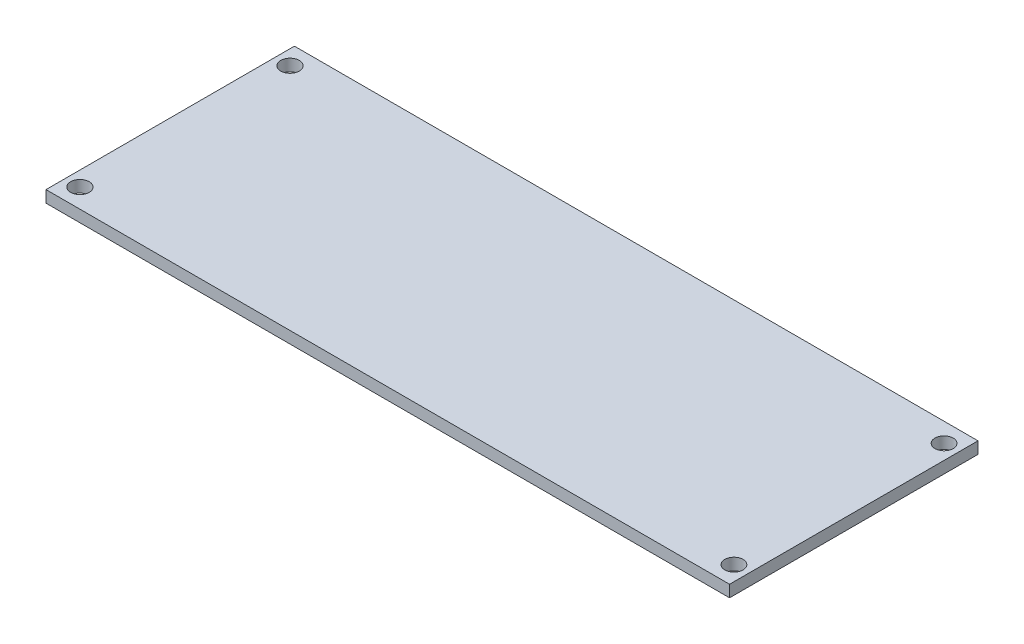
SolidWorks part; units mm, degrees
ref_plane "前视基准面" through (0, 0, 0) normal (0, 0, 1) x (1, 0, 0)
ref_plane "上视基准面" through (0, 0, 0) normal (0, 1, 0) x (1, 0, 0)
ref_plane "右视基准面" through (0, 0, 0) normal (1, 0, 0) x (0, 0, -1)
sketch "草图2" plane through (0, 0, 0) normal (0, 1, 0) x (1, 0, 0)
  line L0 (-58, 21.08) -> (58, 21.08)
  line L1 (-60, 23.08) -> (60, 23.08)
  line L2 (-60, 23.08) -> (-60, -23.08)
  line L3 (-60, -23.08) -> (60, -23.08)
  line L4 (60, 23.08) -> (60, -23.08)
  line L5 (58, 21.08) -> (58, -21.08)
  line L6 (-58, -21.08) -> (58, -21.08)
  line L7 (-58, 21.08) -> (-58, -21.08)
  point P4 (0, 23.08)
  point P6 (60, 0)
  dimension "D1" = 120
  dimension "D2" = 46.16
  dimension "D3" = 2
extrude "凸台-拉伸1" add sketch "草图2" along normal blind 23.1
sketch "草图3" plane through (0, 23.1, 0) normal (0, 1, 0) x (1, 0, 0)
  line L0 (-60, -23.08) -> (60, -23.08) construction
  line L2 (-47.75, 21.05) -> (-47.75, -21.05)
  line L4 (47.75, 21.05) -> (47.75, -21.05)
  line L5 (60, 23.08) -> (-60, 23.08) construction
  line L6 (-42.75, 23.08) -> (-38.75, 23.08)
  line L7 (-42.75, 23.08) -> (-42.75, 17.08)
  line L8 (-42.75, 17.08) -> (-38.75, 17.08)
  line L9 (-38.75, 23.08) -> (-38.75, 17.08)
  line L10 (-42.75, -23.08) -> (-38.75, -23.08)
  line L11 (-42.75, -23.08) -> (-42.75, -17.08)
  line L12 (-42.75, -17.08) -> (-38.75, -17.08)
  line L13 (-38.75, -23.08) -> (-38.75, -17.08)
  line L15 (26.35, 23.08) -> (30.35, 23.08)
  line L16 (26.35, 23.08) -> (26.35, 18.08)
  line L17 (26.35, 18.08) -> (30.35, 18.08)
  line L18 (30.35, 23.08) -> (30.35, 18.08)
  line L19 (26.35, -23.08) -> (30.35, -23.08)
  line L20 (26.35, -23.08) -> (26.35, -18.08)
  line L21 (26.35, -18.08) -> (30.35, -18.08)
  line L22 (30.35, -23.08) -> (30.35, -18.08)
  point P6 (47.75, 0)
  dimension "D1" = 95.5
  dimension "D2" = 42.1
  dimension "D3" = 4
  dimension "D4" = 6
  dimension "D5" = 5
  dimension "D6" = 6
  dimension "D7" = 4
  dimension "D8" = 5
  dimension "D9" = 5
  dimension "D10" = 21.4
  dimension "D11" = 4
  dimension "D12" = 4
  dimension "D13" = 5
  dimension "D14" = 21.4
extrude "凸台-拉伸3" add sketch "草图3" along normal blind 4.1 contours L18 L17 L16 L15 | L22 L21 L20 L19 | L13 L12 L11 L10 | L9 L8 L7 L6
sketch "草图4" plane through (0, 23.1, 0) normal (0, 1, 0) x (1, 0, 0)
  line L0 (-42.75, 21.08) -> (-58, 21.08) construction
  line L1 (-47.75, 21.08) -> (47.75, 21.08)
  line L2 (-47.75, 21.08) -> (-47.75, -21.08)
  line L3 (-47.75, -21.08) -> (47.75, -21.08)
  line L4 (47.75, 21.08) -> (47.75, -21.08)
  line L5 (30.35, -21.08) -> (58, -21.08) construction
  line L6 (60, 23.08) -> (30.35, 23.08) construction
  line L7 (32.55, 23.08) -> (45.75, 23.08)
  line L8 (32.55, 23.08) -> (32.55, 21.08)
  line L9 (32.55, 21.08) -> (45.75, 21.08)
  line L10 (45.75, 23.08) -> (45.75, 21.08)
  line L16 (-38.75, 23.08) -> (-42.75, 23.08)
  line L17 (-42.75, 23.08) -> (-42.75, 17.08)
  line L18 (-42.75, 17.08) -> (-38.75, 17.08)
  line L19 (-38.75, 17.08) -> (-38.75, 23.08)
  line L20 (-58, 21.08) -> (-42.75, 21.08)
  line L21 (-42.75, 21.08) -> (-42.75, 23.08)
  line L22 (-42.75, 23.08) -> (-60, 23.08)
  line L23 (-60, 23.08) -> (-60, -23.08)
  line L24 (-60, -23.08) -> (-42.75, -23.08)
  line L25 (-42.75, -23.08) -> (-42.75, -21.08)
  line L26 (-42.75, -21.08) -> (-58, -21.08)
  line L27 (-58, -21.08) -> (-58, 21.08)
  line L28 (-58, 21.08) -> (-42.75, 21.08)
  line L29 (-42.75, 21.08) -> (-42.75, 23.08)
  line L30 (-42.75, 23.08) -> (-60, 23.08)
  line L31 (-60, 23.08) -> (-60, -23.08)
  line L32 (-60, -23.08) -> (-42.75, -23.08)
  line L33 (-42.75, -23.08) -> (-42.75, -21.08)
  line L34 (-42.75, -21.08) -> (-58, -21.08)
  line L35 (-58, -21.08) -> (-58, 21.08)
  line L36 (-38.75, 23.08) -> (-42.75, 23.08)
  line L37 (-42.75, 23.08) -> (-42.75, 17.08)
  line L38 (-42.75, 17.08) -> (-38.75, 17.08)
  line L39 (-38.75, 17.08) -> (-38.75, 23.08)
  line L40 (-38.75, 23.08) -> (-38.75, 21.08)
  line L41 (-38.75, 21.08) -> (26.35, 21.08)
  line L42 (26.35, 21.08) -> (26.35, 23.08)
  line L43 (26.35, 23.08) -> (-38.75, 23.08)
  line L44 (-38.75, 23.08) -> (-38.75, 21.08)
  line L45 (-38.75, 21.08) -> (26.35, 21.08)
  line L46 (26.35, 21.08) -> (26.35, 23.08)
  line L47 (26.35, 23.08) -> (-38.75, 23.08)
  line L48 (30.35, 23.08) -> (26.35, 23.08)
  line L49 (26.35, 23.08) -> (26.35, 18.08)
  line L50 (26.35, 18.08) -> (30.35, 18.08)
  line L51 (30.35, 18.08) -> (30.35, 23.08)
  line L52 (30.35, 23.08) -> (26.35, 23.08)
  line L53 (26.35, 23.08) -> (26.35, 18.08)
  line L54 (26.35, 18.08) -> (30.35, 18.08)
  line L55 (30.35, 18.08) -> (30.35, 23.08)
  line L56 (26.35, -23.08) -> (30.35, -23.08)
  line L57 (30.35, -23.08) -> (30.35, -18.08)
  line L58 (30.35, -18.08) -> (26.35, -18.08)
  line L59 (26.35, -18.08) -> (26.35, -23.08)
  line L60 (58, -21.08) -> (30.35, -21.08)
  line L61 (30.35, -21.08) -> (30.35, -23.08)
  line L62 (30.35, -23.08) -> (60, -23.08)
  line L63 (60, -23.08) -> (60, 23.08)
  line L64 (60, 23.08) -> (30.35, 23.08)
  line L65 (30.35, 23.08) -> (30.35, 21.08)
  line L66 (30.35, 21.08) -> (58, 21.08)
  line L67 (58, 21.08) -> (58, -21.08)
  line L68 (58, -21.08) -> (30.35, -21.08)
  line L69 (30.35, -21.08) -> (30.35, -23.08)
  line L70 (30.35, -23.08) -> (60, -23.08)
  line L71 (60, -23.08) -> (60, 23.08)
  line L72 (60, 23.08) -> (30.35, 23.08)
  line L73 (30.35, 23.08) -> (30.35, 21.08)
  line L74 (30.35, 21.08) -> (58, 21.08)
  line L75 (58, 21.08) -> (58, -21.08)
  line L76 (26.35, -23.08) -> (30.35, -23.08)
  line L77 (30.35, -23.08) -> (30.35, -18.08)
  line L78 (30.35, -18.08) -> (26.35, -18.08)
  line L79 (26.35, -18.08) -> (26.35, -23.08)
  line L81 (22.55, 23.08) -> (15.05, 23.08)
  line L82 (22.55, 23.08) -> (22.55, 21.08)
  line L83 (22.55, 21.08) -> (15.05, 21.08)
  line L87 (26.35, -21.08) -> (-38.75, -21.08)
  line L88 (-38.75, -21.08) -> (-38.75, -23.08)
  line L89 (-38.75, -23.08) -> (26.35, -23.08)
  line L90 (26.35, -23.08) -> (26.35, -21.08)
  line L91 (26.35, -21.08) -> (-38.75, -21.08)
  line L92 (-42.75, -23.08) -> (-38.75, -23.08)
  line L93 (-38.75, -23.08) -> (-38.75, -17.08)
  line L94 (-38.75, -17.08) -> (-42.75, -17.08)
  line L95 (-42.75, -17.08) -> (-42.75, -23.08)
  line L96 (-42.75, -23.08) -> (-38.75, -23.08)
  line L97 (-38.75, -23.08) -> (-38.75, -17.08)
  line L98 (-38.75, -17.08) -> (-42.75, -17.08)
  line L99 (-42.75, -17.08) -> (-42.75, -23.08)
  line L100 (15.05, 23.08) -> (15.05, 21.08)
  line L101 (-38.75, -21.08) -> (-38.75, -23.08)
  line L102 (-38.75, -23.08) -> (26.35, -23.08)
  line L103 (26.35, -23.08) -> (26.35, -21.08)
  point P8 (0, 21.08)
  line M45 (58, -21.08) -> (30.35, -21.08)
  line M46 (30.35, -21.08) -> (30.35, -23.08)
  line M47 (30.35, -23.08) -> (60, -23.08)
  line M48 (60, -23.08) -> (60, 23.08)
  line M49 (60, 23.08) -> (30.35, 23.08)
  line M50 (30.35, 23.08) -> (30.35, 21.08)
  line M51 (30.35, 21.08) -> (58, 21.08)
  line M52 (58, 21.08) -> (58, -21.08)
  dimension "D1" = 95.5
  dimension "D2" = 2
  dimension "D3" = 13.2
  dimension "D12" = 25.2
  dimension "D13" = 7.5
  dimension "D4" = 0
  dimension "D5" = 0
  dimension "D6" = 0
  dimension "D7" = 0
  dimension "D8" = 0
  dimension "D9" = 0
  dimension "D10" = 0
  dimension "D11" = 0
extrude "凸台-拉伸4" add sketch "草图4" along normal blind 5.5 contours L34 L35 L28 L1 L29 L30 L31 L32 L33 L3 | L96 L97 L3 L33 | L97 L102 L79 L3 | L3 L79 L76 M46 | L10 M49 M51 M52 M45 M46 M47 M48 | L8 M49 M50 M51 | L52 L46 L1 M50 | L47 L82 L45 L46 | L100 L47 L39 L1 | L1 L39 L36 L29 region at (-52.875, 23.1, -21.5728) region at (-40.75, 23.1, -22.08) region at (-11.85, 23.1, -22.08) region at (-40.75, 23.1, 22.08) region at (-6.2, 23.1, 22.08) region at (24.45, 23.1, -22.08) region at (28.35, 23.1, 22.08) region at (28.35, 23.1, -22.08) region at (39.05, 23.1, 21.6286) region at (31.45, 23.1, -22.08)
sketch "草图7" plane through (0, 0, -21.08) normal (0, 0, 1) x (1, 0, 0)
  line L1 (22.55, 28.6) -> (15.05, 28.6)
  line L2 (22.55, 28.6) -> (22.55, 26.6)
  line L3 (22.55, 26.6) -> (15.05, 26.6)
  line L4 (15.05, 28.6) -> (15.05, 26.6)
  line L12 (22.55, 23.1) -> (15.05, 23.1)
  line L13 (15.05, 23.1) -> (15.05, 28.6)
  line L14 (15.05, 28.6) -> (-58, 28.6)
  line L15 (-58, 28.6) -> (-58, 0)
  line L16 (-58, 0) -> (58, 0)
  line L17 (58, 0) -> (58, 28.6)
  line L18 (58, 28.6) -> (45.75, 28.6)
  line L19 (45.75, 28.6) -> (45.75, 23.1)
  line L20 (45.75, 23.1) -> (32.55, 23.1)
  line L21 (32.55, 23.1) -> (32.55, 28.6)
  line L22 (32.55, 28.6) -> (22.55, 28.6)
  line L23 (22.55, 28.6) -> (22.55, 23.1)
  line L24 (22.55, 23.1) -> (15.05, 23.1)
  line L25 (15.05, 23.1) -> (15.05, 28.6)
  line L26 (15.05, 28.6) -> (-58, 28.6)
  line L27 (-58, 28.6) -> (-58, 0)
  line L28 (-58, 0) -> (58, 0)
  line L29 (58, 0) -> (58, 28.6)
  line L30 (58, 28.6) -> (45.75, 28.6)
  line L31 (45.75, 28.6) -> (45.75, 23.1)
  line L32 (45.75, 23.1) -> (32.55, 23.1)
  line L33 (32.55, 23.1) -> (32.55, 28.6)
  line L34 (32.55, 28.6) -> (22.55, 28.6)
  line L35 (22.55, 28.6) -> (22.55, 23.1)
  line M15 (15.05, 23.1) -> (15.05, 28.6)
  line M25 (22.55, 28.6) -> (22.55, 23.1)
  dimension "D2" = 2
  dimension "D1" = 0
extrude "凸台-拉伸5" add sketch "草图7" against normal blind 1 contours L3 L1 M25 M15 region at (18.8, 27.6, -21.08)
sketch "草图8" plane through (0, 0, -23.08) normal (0, 0, -1) x (-1, 0, 0)
  line L1 (-22.55, 23.1) -> (-15.05, 23.1)
  line L2 (-22.55, 23.1) -> (-22.55, 21.1)
  line L3 (-22.55, 21.1) -> (-15.05, 21.1)
  line L4 (-15.05, 23.1) -> (-15.05, 21.1)
  line L5 (-22.55, 28.6) -> (-26.55, 28.6)
  line L6 (-22.55, 28.6) -> (-22.55, 21.1)
  line L7 (-22.55, 21.1) -> (-26.55, 21.1)
  line L8 (-26.55, 28.6) -> (-26.55, 21.1)
  line L9 (-15.05, 28.6) -> (-11.05, 28.6)
  line L10 (-15.05, 28.6) -> (-15.05, 21.1)
  line L11 (-15.05, 21.1) -> (-11.05, 21.1)
  line L12 (-11.05, 28.6) -> (-11.05, 21.1)
  line M4 (-15.05, 28.6) -> (-15.05, 23.1)
  line M5 (-15.05, 23.1) -> (-22.55, 23.1)
  line M6 (-22.55, 23.1) -> (-22.55, 28.6)
  line M7 (-22.55, 28.6) -> (-32.55, 28.6)
  line M15 (60, 28.6) -> (-15.05, 28.6)
  dimension "D1" = 2
  dimension "D2" = 4
  dimension "D3" = 4
extrude "切除-拉伸1" cut sketch "草图8" against normal blind 1 contours L8 L7 L2 M7 M6 | L4 L2 L3 M5 | L12 L4 L11 M15 M4 region at (18.8, 22.1, -23.08) region at (24.55, 24.85, -23.08) region at (13.05, 24.85, -23.08)
sketch "草图9" plane through (0, 28.6, 0) normal (0, 1, 0) x (1, 0, 0)
  line L0 (18.8, 22.6917) -> (18.8, 20.4523)
  line L4 (22.55, 21.08) -> (22.55, 22.08)
  line L5 (22.55, 22.08) -> (15.05, 22.08)
  line L6 (15.05, 22.08) -> (15.05, 21.08)
  line L7 (15.05, 21.08) -> (22.55, 21.08)
  line L8 (22.55, 21.08) -> (22.55, 22.08)
  line L9 (22.55, 22.08) -> (15.05, 22.08)
  line L10 (15.05, 22.08) -> (15.05, 21.08)
  line L11 (15.05, 21.08) -> (22.55, 21.08)
  spline S0 degree 2 poles (11.05, 23.08) (12.6234, 21.9645) (15.05, 22.08) knots 0 0 0 1 1 1
  spline S1 degree 2 poles (26.55, 23.08) (24.9766, 21.9645) (22.55, 22.08) knots 0 0 0 1 1 1
  point P5 (18.8, 22.08)
  line M6 (26.55, 23.08) -> (26.55, 22.08)
  line M7 (26.55, 22.08) -> (11.05, 22.08)
  line M8 (11.05, 22.08) -> (11.05, 23.08)
  dimension "D1" = 0
extrude "凸台-拉伸6" add sketch "草图9" against normal up to surface (7.5 mm away) contours S0 M8 M7 | S1 M6 M7 region at (25.7395, 28.6, -22.3711) region at (11.8605, 28.6, -22.3711) up to face at (18.8, 21.1, -22.58)
sketch "草图10" plane through (0, 28.6, 0) normal (0, 1, 0) x (1, 0, 0)
  line L1 (-60, 23.08) -> (60, 23.08)
  line L2 (-60, 23.08) -> (-60, -23.08)
  line L3 (-60, -23.08) -> (60, -23.08)
  line L4 (60, 23.08) -> (60, -23.08)
  line L5 (-58, 21.08) -> (58, 21.08)
  line L6 (-58, 21.08) -> (-58, -21.08)
  line L7 (-58, -21.08) -> (58, -21.08)
  line L8 (58, 21.08) -> (58, -21.08)
extrude "凸台-拉伸7" add sketch "草图10" along normal blind 2
sketch "草图11" plane through (0, 0, -21.08) normal (0, 0, 1) x (1, 0, 0)
  line L0 (45.75, 23.1) -> (32.55, 23.1) construction
  line L1 (45.75, 23.1) -> (32.55, 23.1)
  line L2 (58, 0) -> (-58, 0) construction
  line L3 (36.11, 23.1) -> (39.11, 23.1)
  line L4 (36.11, 23.1) -> (36.11, 0)
  line L5 (36.11, 0) -> (39.11, 0)
  line L6 (39.11, 23.1) -> (39.11, 0)
  line M6 (-58, 0) -> (58, 0)
  dimension "D1" = 9.64
  dimension "D2" = 3
extrude "切除-拉伸2" cut sketch "草图11" against normal blind 1.5 contours L6 L1 L4 M6 region at (37.61, 11.55, -21.08)
sketch "草图12" plane through (0, 30.6, 0) normal (0, 1, 0) x (1, 0, 0)
  line L1 (-60, 23.08) -> (60, 23.08)
  line L2 (-60, 23.08) -> (-60, -23.08)
  line L3 (-60, -23.08) -> (60, -23.08)
  line L4 (60, 23.08) -> (60, -23.08)
extrude "凸台-拉伸8" add sketch "草图12" along normal blind 2
sketch "草图13" plane through (0, 32.6, 0) normal (0, 1, 0) x (1, 0, 0)
  line L0 (-58, 21.08) -> (-58, -21.08) construction
  line L1 (58, -21.08) -> (58, 21.08) construction
  line L2 (-58, -21.08) -> (58, -21.08) construction
  line L3 (36.11, 21.08) -> (-58, 21.08) construction
  line L4 (-58, 21.08) -> (-58, -21.08)
  line L5 (58, -21.08) -> (58, 21.08)
  line L6 (-58, -21.08) -> (58, -21.08)
  line L7 (36.11, 21.08) -> (-58, 21.08)
  line L8 (36.11, 21.08) -> (58, 21.08)
  line L10 (-58, 21.08) -> (58, 21.08)
  line L11 (-58, 21.08) -> (-58, 8.08)
  line L12 (-58, 8.08) -> (58, 8.08)
  line L13 (58, 21.08) -> (58, 8.08)
  circle A0 centre (38.25, -12.68) radius 3.5
  dimension "D2" = 7
  dimension "D1" = 13
  dimension "D3" = 19.75
  dimension "D4" = 8.4
extrude "切除-拉伸3" cut sketch "草图13" against normal blind 2 contours L4 L12 L5 L8 L7 | A0 region at (0, 32.6, -14.58) region at (38.25, 32.6, 12.68)
sketch "草图14" plane through (-58, 0, 0) normal (1, 0, 0) x (0, 0, -1)
  line L0 (30.1627, 64.1374) -> (36.3882, 59.7782)
  line L1 (8.08, 32.6) -> (30.1627, 64.1374)
  line L2 (36.3882, 59.7782) -> (17.3579, 32.6)
  line L3 (19.7994, 32.6) -> (38.6001, 59.4502)
  line L4 (19.7994, 32.6) -> (17.3579, 32.6)
  line L5 (38.6001, 59.4502) -> (29.9171, 65.5301)
  line L6 (29.9171, 65.5301) -> (6.8592, 32.6)
  line L7 (-21.08, 0) -> (21.08, 0)
  line L8 (21.08, 0) -> (21.08, 32.6)
  line L9 (21.08, 32.6) -> (8.08, 32.6)
  line L10 (8.08, 32.6) -> (8.08, 30.6)
  line L11 (8.08, 30.6) -> (-21.08, 30.6)
  line L12 (-21.08, 30.6) -> (-21.08, 0)
  line L15 (19.7994, 32.6) -> (8.08, 32.6)
  line L19 (6.8592, 32.6) -> (8.08, 32.6)
  line L20 (8.08, 32.6) -> (6.8592, 32.6)
  line M14 (21.08, 32.6) -> (8.08, 32.6)
  dimension "D2" = 38.5
  dimension "D3" = 7.6
  dimension "D4" = 2
  dimension "D5" = 1
  dimension "D6" = 55
  dimension "D7" = 1
  dimension "D1" = 0
extrude "凸台-拉伸15" add sketch "草图14" along normal up to surface (116 mm away) separate body contours L6 L19 L1 L0 L2 L3 L5 M14 region at (-58, 48.631, -18.7467) up to face at (58, 21.0667, -2.6933)
sketch "草图15" plane through (58, 0, 0) normal (1, 0, 0) x (0, 0, -1)
  line L0 (19.7994, 32.6) -> (6.8592, 32.6)
  line L8 (6.8592, 32.6) -> (8.08, 32.6)
  line L9 (8.08, 32.6) -> (30.1627, 64.1374)
  line L10 (30.1627, 64.1374) -> (36.3882, 59.7782)
  line L11 (36.3882, 59.7782) -> (17.3579, 32.6)
  line L12 (17.3579, 32.6) -> (19.7994, 32.6)
  line L13 (19.7994, 32.6) -> (38.6001, 59.4502)
  line L14 (38.6001, 59.4502) -> (29.9171, 65.5301)
  line L15 (29.9171, 65.5301) -> (6.8592, 32.6)
  line L16 (6.8592, 32.6) -> (8.08, 32.6)
  line L17 (8.08, 32.6) -> (30.1627, 64.1374)
  line L18 (30.1627, 64.1374) -> (36.3882, 59.7782)
  line L19 (36.3882, 59.7782) -> (17.3579, 32.6)
  line L20 (17.3579, 32.6) -> (19.7994, 32.6)
  line L21 (19.7994, 32.6) -> (38.6001, 59.4502)
  line L22 (38.6001, 59.4502) -> (29.9171, 65.5301)
  line L23 (29.9171, 65.5301) -> (6.8592, 32.6)
  line M9 (6.8592, 32.6) -> (8.08, 32.6)
  line M10 (8.08, 32.6) -> (30.1627, 64.1374)
  line M11 (30.1627, 64.1374) -> (36.3882, 59.7782)
  line M12 (36.3882, 59.7782) -> (17.3579, 32.6)
  line M13 (17.3579, 32.6) -> (19.7994, 32.6)
  line M14 (19.7994, 32.6) -> (38.6001, 59.4502)
  line M15 (38.6001, 59.4502) -> (29.9171, 65.5301)
  line M16 (29.9171, 65.5301) -> (6.8592, 32.6)
  dimension "D1" = 0
extrude "凸台-拉伸17" add sketch "草图15" along normal up to surface (2 mm away) separate body contours M16 M9 M10 M11 M12 M13 M14 M15 | L0 M12 M11 M10 region at (58, 33.0574, -18.5787) region at (58, 47.3059, -22.9013) up to face at (60, 16.3, 0)
sketch "草图16" plane through (-58, 0, 0) normal (-1, 0, 0) x (0, 0, 1)
  line L0 (-19.7994, 32.6) -> (-6.8592, 32.6)
  line L8 (-6.8592, 32.6) -> (-29.9171, 65.5301)
  line L9 (-29.9171, 65.5301) -> (-38.6001, 59.4502)
  line L10 (-38.6001, 59.4502) -> (-19.7994, 32.6)
  line L11 (-19.7994, 32.6) -> (-17.3579, 32.6)
  line L12 (-17.3579, 32.6) -> (-36.3882, 59.7782)
  line L13 (-36.3882, 59.7782) -> (-30.1627, 64.1374)
  line L14 (-30.1627, 64.1374) -> (-8.08, 32.6)
  line L15 (-8.08, 32.6) -> (-6.8592, 32.6)
  line L16 (-6.8592, 32.6) -> (-29.9171, 65.5301)
  line L17 (-29.9171, 65.5301) -> (-38.6001, 59.4502)
  line L18 (-38.6001, 59.4502) -> (-19.7994, 32.6)
  line L19 (-19.7994, 32.6) -> (-17.3579, 32.6)
  line L20 (-17.3579, 32.6) -> (-36.3882, 59.7782)
  line L21 (-36.3882, 59.7782) -> (-30.1627, 64.1374)
  line L22 (-30.1627, 64.1374) -> (-8.08, 32.6)
  line L23 (-8.08, 32.6) -> (-6.8592, 32.6)
  line M9 (-6.8592, 32.6) -> (-29.9171, 65.5301)
  line M10 (-29.9171, 65.5301) -> (-38.6001, 59.4502)
  line M11 (-38.6001, 59.4502) -> (-19.7994, 32.6)
  line M12 (-19.7994, 32.6) -> (-17.3579, 32.6)
  line M13 (-17.3579, 32.6) -> (-36.3882, 59.7782)
  line M14 (-36.3882, 59.7782) -> (-30.1627, 64.1374)
  line M15 (-30.1627, 64.1374) -> (-8.08, 32.6)
  line M16 (-8.08, 32.6) -> (-6.8592, 32.6)
  dimension "D1" = 0
extrude "凸台-拉伸18" add sketch "草图16" along normal up to surface (2 mm away) separate body contours L0 M13 M15 M14 | M16 M9 M10 M11 M12 M13 M14 M15 region at (-58, 46.2874, -28.8251) region at (-58, 47.3059, -22.9013) up to face at (-60, 16.3, 0)
sketch "草图17" plane through (-60, 0, 0) normal (-1, 0, 0) x (0, 0, 1)
  line L0 (-23.08, 32.6) -> (-23.08, 37.2851)
  line L1 (-19.7994, 32.6) -> (-38.6001, 59.4502) construction
  line L2 (-23.08, 32.6) -> (-23.08, 30.3029)
  line L3 (-23.08, 32.6) -> (-23.08, 0) construction
  line L4 (-23.08, 30.3029) -> (-19.7994, 32.6)
  line L5 (-19.7994, 32.6) -> (-23.08, 37.2851)
extrude "凸台-拉伸19" add sketch "草图17" against normal up to surface (120 mm away) up to face at (60, 16.3, 0)
sketch "草图18" plane through (58, 0, 0) normal (-1, 0, 0) x (0, 0, 1)
  line L1 (-8.08, 32.6) -> (-5.3341, 28.6785)
  line L2 (-5.3341, 28.6785) -> (-9.4039, 25.8288)
  line L3 (-9.4039, 25.8288) -> (-8.08, 32.6)
extrude "切除-拉伸4" cut sketch "草图18" along normal up to surface (116 mm away) up to face at (-58, 31.4619, -11.9868)
sketch "草图19" plane through (0, 7.5023, 10.7144) normal (0, 0.5736, 0.8192) x (1, 0, 0)
  line L1 (-45, 64.1181) -> (45, 64.1181)
  line L2 (-45, 64.1181) -> (-45, 34.6181)
  line L3 (-45, 34.6181) -> (45, 34.6181)
  line L4 (58, 69.8389) -> (-58, 69.8389)
  line L5 (58, 28.8973) -> (58, 69.8389)
  line L6 (-58, 28.8973) -> (58, 28.8973)
  line L7 (-58, 69.8389) -> (-58, 28.8973)
  line L8 (58, 69.8389) -> (-58, 69.8389)
  line L9 (58, 28.8973) -> (58, 69.8389)
  line L10 (-58, 28.8973) -> (58, 28.8973)
  line L11 (-58, 69.8389) -> (-58, 28.8973)
  line L12 (45, 64.1181) -> (45, 34.6181)
  line L13 (-31.5, 34.6181) -> (31.5, 34.6181)
  line L14 (-31.5, 34.6181) -> (-31.5, 32.0181)
  line L15 (-31.5, 32.0181) -> (31.5, 32.0181)
  line L16 (31.5, 34.6181) -> (31.5, 32.0181)
  point P8 (0, 64.1181)
  point P9 (0, 69.8389)
  point P10 (-45, 49.3681)
  point P11 (-58, 49.3681)
  point P16 (0, 32.0181)
  point P17 (0, 34.6181)
  dimension "D2" = 90
  dimension "D3" = 29.5
  dimension "D4" = 2.6
  dimension "D5" = 63
  dimension "D1" = 0
extrude "切除-拉伸5" cut sketch "草图19" against normal up to next contours L12 L1 L2 L3 | L16 L3 L14 L15 region at (0, 47.9423, -17.602) region at (0, 34.7949, -8.3961)
sketch "草图20" plane through (0, 58.0278, -40.6315) normal (0, 0.8192, -0.5736) x (1, 0, 0)
  line L4 (-60, -13.0798) -> (60, -13.0798)
  line L5 (60, -13.0798) -> (60, -2.4798)
  line L6 (60, -2.4798) -> (-60, -2.4798)
  line L7 (-60, -2.4798) -> (-60, -13.0798)
  line L8 (-60, -13.0798) -> (60, -13.0798)
  line L9 (60, -13.0798) -> (60, -2.4798)
  line L10 (60, -2.4798) -> (-60, -2.4798)
  line L11 (-60, -2.4798) -> (-60, -13.0798)
  dimension "D1" = 0
extrude "凸台-拉伸20" add sketch "草图20" against normal blind 5.5
sketch "草图21" plane through (0, 53.5225, -37.4768) normal (0, -0.8192, 0.5736) x (1, 0, 0)
  line L0 (-45, 13.0798) -> (45, 13.0798) construction
  line L1 (50.25, 12.0798) -> (-50.25, 12.0798)
  line L2 (50.25, 12.0798) -> (50.25, 10.4598)
  line L3 (50.25, 10.4598) -> (-50.25, 10.4598)
  line L4 (58, 4.4798) -> (58, 12.0798)
  line L5 (58, 12.0798) -> (-58, 12.0798)
  line L6 (-58, 12.0798) -> (-58, 4.4798)
  line L7 (-58, 4.4798) -> (58, 4.4798)
  line L8 (58, 4.4798) -> (58, 12.0798)
  line L9 (58, 12.0798) -> (-58, 12.0798)
  line L10 (-58, 12.0798) -> (-58, 4.4798)
  line L11 (-58, 4.4798) -> (58, 4.4798)
  line L12 (-50.25, 12.0798) -> (-50.25, 10.4598)
  line L13 (-45, 13.0798) -> (45, 13.0798)
  point P10 (0, 13.0798)
  point P11 (0, 10.4598)
  line M8 (58, 12.0798) -> (-58, 12.0798)
  dimension "D2" = 1.62
  dimension "D3" = 100.5
  dimension "D1" = 0
extrude "切除-拉伸6" cut sketch "草图21" against normal blind 5.5 contours L12 L3 L2 M8 region at (0, 59.9866, -28.2451)
sketch "草图22" plane through (0, 58.0278, -40.6315) normal (0, 0.8192, -0.5736) x (1, 0, 0)
  line L1 (60, -2.4798) -> (-60, -2.4798)
  line L2 (60, -2.4798) -> (60, -13.0798)
  line L3 (60, -13.0798) -> (-60, -13.0798)
  line L4 (-60, -2.4798) -> (-60, -13.0798)
extrude "凸台-拉伸21" add sketch "草图22" along normal blind 1
sketch "草图23" plane through (50.25, 0, 0) normal (-1, 0, 0) x (0, 0, 1)
  line L0 (-28.9086, 59.522) -> (-30.5029, 57.9277)
  line L1 (-30.5029, 57.9277) -> (-30.6836, 62.4834)
  line L2 (-30.6836, 62.4834) -> (-28.9086, 59.522)
extrude "切除-拉伸8" cut sketch "草图23" along normal up to surface (100.5 mm away) up to face at (-50.25, 62.2392, -29.8224)
sketch "草图24" plane through (58, 0, 0) normal (-1, 0, 0) x (0, 0, 1)
  line L0 (-9.1066, 11.2099) -> (-12.1529, 11.2099)
  line L1 (6.9916, 11.2099) -> (10.0379, 11.2099)
  circle A0 centre (-10.6298, 8.5099) radius 3.1
  circle A1 centre (8.5148, 8.5099) radius 3.1
  point P8 (-10.6298, 11.2099)
  dimension "D1" = 6.2
  dimension "D2" = 6.2
  dimension "D3" = 2.7
extrude "切除-拉伸10" cut sketch "草图24" against normal up to surface (2 mm away) contours L1 A1 | L0 A0 region at (58, 8.4296, -10.6298) region at (58, 8.4296, 8.5148) up to face at (60, 32.7291, -10.9319)
sketch "草图29" plane through (0, 23.1, 0) normal (0, -1, 0) x (1, 0, 0)
  line L0 (26.35, 21.08) -> (30.35, 21.08) construction
  line L1 (-47.75, 21.08) -> (47.75, 21.08)
  line L2 (-47.75, 21.08) -> (-47.75, -21.08)
  line L3 (-47.75, -21.08) -> (47.75, -21.08)
  line L4 (47.75, 21.08) -> (47.75, -21.08)
  line L5 (-58, 21.08) -> (58, 21.08) construction
  line L6 (36.11, -21.08) -> (-58, -21.08) construction
  line L7 (26.35, 18.08) -> (30.35, 18.08) construction
  line L8 (47.75, 21.08) -> (51.75, 21.08)
  line L9 (47.75, 21.08) -> (47.75, 18.08)
  line L10 (47.75, 18.08) -> (51.75, 18.08)
  line L11 (51.75, 21.08) -> (51.75, 18.08)
  line L13 (47.75, -21.08) -> (51.75, -21.08)
  line L14 (47.75, -21.08) -> (47.75, -18.08)
  line L15 (47.75, -18.08) -> (51.75, -18.08)
  line L16 (51.75, -21.08) -> (51.75, -18.08)
  line L17 (-47.75, 21.08) -> (-51.75, 21.08)
  line L18 (-47.75, 21.08) -> (-47.75, 18.08)
  line L19 (-47.75, 18.08) -> (-51.75, 18.08)
  line L20 (-51.75, 21.08) -> (-51.75, 18.08)
  line L21 (-47.75, -21.08) -> (-51.75, -21.08)
  line L22 (-47.75, -21.08) -> (-47.75, -18.08)
  line L23 (-47.75, -18.08) -> (-51.75, -18.08)
  line L24 (-51.75, -21.08) -> (-51.75, -18.08)
  point P6 (0, 21.08)
  point P9 (0, 21.08)
  dimension "D1" = 95.5
  dimension "D2" = 4
  dimension "D3" = 4
  dimension "D4" = 3
  dimension "D5" = 3
  dimension "D6" = 4
  dimension "D7" = 3
  dimension "D8" = 4
extrude "凸台-拉伸23" add sketch "草图29" along normal up to surface (23.1 mm away) contours L18 L19 L20 L17 | L22 L23 L24 L21 | L9 L10 L11 L8 | L14 L15 L16 L13 up to face at (0, 0, 0)
sketch "草图31" plane through (0, 0, 0) normal (0, -1, 0) x (1, 0, 0)
  line L0 (-51.75, 18.08) -> (-51.75, 21.08) construction
  line L1 (-58, 21.08) -> (-51.75, 21.08)
  line L2 (-58, 21.08) -> (-58, 14.83)
  line L3 (-58, 14.83) -> (-51.75, 14.83)
  line L4 (-51.75, 21.08) -> (-51.75, 14.83)
  line L6 (-58, -21.08) -> (-51.75, -21.08)
  line L7 (-58, -21.08) -> (-58, -14.83)
  line L8 (-58, -14.83) -> (-51.75, -14.83)
  line L9 (-51.75, -21.08) -> (-51.75, -14.83)
  line L10 (58, 21.08) -> (51.7445, 21.08)
  line L11 (58, 21.08) -> (58, 14.83)
  line L12 (58, 14.83) -> (51.7445, 14.83)
  line L13 (51.7445, 21.08) -> (51.7445, 14.83)
  line L14 (58, -21.08) -> (51.7445, -21.08)
  line L15 (58, -21.08) -> (58, -14.83)
  line L16 (58, -14.83) -> (51.7445, -14.83)
  line L17 (51.7445, -21.08) -> (51.7445, -14.83)
  dimension "D1" = 6.25
  dimension "D2" = 6.25
  dimension "D3" = 6.25
  dimension "D4" = 6.2555
  dimension "D5" = 6.2555
  dimension "D6" = 6.25
extrude "凸台-拉伸24" add sketch "草图31" against normal blind 6
sketch "草图33" plane through (0, 0, -14.83) normal (0, 0, 1) x (1, 0, 0)
  line L1 (-58.4922, 4.9036) -> (-52.4922, 4.9036)
  line L2 (-58.4922, 4.9036) -> (-58.4922, 2.2036)
  line L3 (-58.4922, 2.2036) -> (-52.4922, 2.2036)
  line L4 (-52.4922, 4.9036) -> (-52.4922, 2.2036)
  line L6 (60, 0) -> (-60, 0) construction
  line L7 (60, 0) -> (-60, 0)
  line L8 (0, 18.228) -> (0, -18.228)
  line L9 (58.4922, 4.9036) -> (58.4922, 2.2036)
  line L10 (58.4922, 2.2036) -> (52.4922, 2.2036)
  line L11 (52.4922, 4.9036) -> (52.4922, 2.2036)
  line L12 (58.4922, 4.9036) -> (52.4922, 4.9036)
  point P4 (0, 0)
  point P9 (0, 0)
  line M9 (-58, 6) -> (-58, 0)
  dimension "D1" = 6
  dimension "D2" = 2.7
extrude "切除-拉伸11" cut sketch "草图33" against normal blind 6 contours L4 L1 L3 M9 | L9 L12 L11 L10 region at (-55.2461, 3.5536, -14.83) region at (55.4922, 3.5536, -14.83)
sketch "草图34" plane through (-58, 0, 0) normal (1, 0, 0) x (0, 0, -1)
  line L1 (20.83, 4.9036) -> (7.4453, 4.9036)
  line L2 (20.83, 4.9036) -> (20.83, 2.2036)
  line L3 (20.83, 2.2036) -> (7.4453, 2.2036)
  line L4 (7.4453, 4.9036) -> (7.4453, 2.2036)
extrude "切除-拉伸12" cut sketch "草图34" against normal blind 0.5
sketch "草图35" plane through (0, 0, -14.83) normal (0, 0, 1) x (1, 0, 0)
  line L4 (58.4922, 2.2036) -> (58.4922, 4.9036)
  line L5 (58.4922, 4.9036) -> (52.4922, 4.9036)
  line L6 (52.4922, 4.9036) -> (52.4922, 2.2036)
  line L7 (52.4922, 2.2036) -> (58.4922, 2.2036)
  line L8 (58.4922, 2.2036) -> (58.4922, 4.9036)
  line L9 (58.4922, 4.9036) -> (52.4922, 4.9036)
  line L10 (52.4922, 4.9036) -> (52.4922, 2.2036)
  line L11 (52.4922, 2.2036) -> (58.4922, 2.2036)
  dimension "D1" = 0
extrude "切除-拉伸13" cut sketch "草图35" along normal blind 6.5
sketch "草图36" plane through (0, 0, 0) normal (0, -1, 0) x (1, 0, 0)
  line L1 (-52.4922, -14.83) -> (-58.5, -14.83)
  line L2 (-52.4922, -14.83) -> (-52.4922, -20.83)
  line L3 (-52.4922, -20.83) -> (-58.5, -20.83)
  line L4 (-58.5, -14.83) -> (-58.5, -20.83)
  line L5 (52.4922, -20.83) -> (58.4922, -20.83)
  line L6 (-52.4922, -14.83) -> (-58, -14.83)
  line L7 (-58, -14.83) -> (-58, -7.4453)
  line L8 (-58, -7.4453) -> (-58.5, -7.4453)
  line L9 (-58.5, -7.4453) -> (-58.5, -20.83)
  line L10 (-58.5, -20.83) -> (-52.4922, -20.83)
  line L11 (-52.4922, -20.83) -> (-52.4922, -14.83)
  line L12 (-52.4922, -14.83) -> (-58, -14.83)
  line L13 (-58, -14.83) -> (-58, -7.4453)
  line L14 (-58, -7.4453) -> (-58.5, -7.4453)
  line L15 (-58.5, -7.4453) -> (-58.5, -20.83)
  line L16 (-58.5, -20.83) -> (-52.4922, -20.83)
  line L17 (-52.4922, -20.83) -> (-52.4922, -14.83)
  line L18 (52.4922, -20.83) -> (52.4922, -14.83)
  line L19 (52.4922, -14.83) -> (58.4922, -14.83)
  line L20 (58.4922, -20.83) -> (58.4922, -14.83)
  line L22 (58.4922, -20.83) -> (58.4922, -8.33)
  line L23 (58.4922, -8.33) -> (58, -8.33)
  line L24 (58, -8.33) -> (58, -14.83)
  line L25 (58, -14.83) -> (52.4922, -14.83)
  line L26 (52.4922, -14.83) -> (52.4922, -20.83)
  line L27 (52.4922, -20.83) -> (58.4922, -20.83)
  line L28 (58.4922, -20.83) -> (58.4922, -8.33)
  line L29 (58.4922, -8.33) -> (58, -8.33)
  line L30 (58, -8.33) -> (58, -14.83)
  line L31 (58, -14.83) -> (52.4922, -14.83)
  line L32 (52.4922, -14.83) -> (52.4922, -20.83)
  line L33 (52.4922, -20.83) -> (58.4922, -20.83)
  circle A0 centre (-55.4961, -17.83) radius 1.575
  circle A1 centre (55.4922, -17.83) radius 1.55
  point P10 (-55.4961, -20.83)
  point P11 (-52.4922, -17.83)
  point P21 (55.4922, -20.83)
  point P22 (58.4922, -17.83)
  dimension "D2" = 3.15
  dimension "D4" = 3.1
  dimension "D1" = 0
  dimension "D3" = 0
extrude "切除-拉伸14" cut sketch "草图36" against normal blind 6.5 contours A1 | A0 region at (-55.4961, 0, -17.83) region at (55.4922, 0, -17.83)
sketch "草图37" plane through (0, 0, 0) normal (0, -1, 0) x (1, 0, 0)
  line L0 (60, 23.08) -> (60, -23.08) construction
  line L1 (60, 23.08) -> (60, -23.08)
  line L2 (-60, -23.08) -> (-60, 23.08) construction
  line L3 (-60, -23.08) -> (-60, 23.08)
  line L4 (-118.3776, 0) -> (81.3435, 0)
  circle A0 centre (55.4922, -17.83) radius 1.55 construction
  circle A1 centre (55.4922, -17.83) radius 1.55
  circle A2 centre (-55.4961, -17.83) radius 1.575 construction
  circle A3 centre (-55.4961, -17.83) radius 1.575
  circle A4 centre (55.4922, 17.83) radius 1.55
  circle A5 centre (-55.4961, 17.83) radius 1.575
extrude "切除-拉伸15" cut sketch "草图37" against normal blind 6.5 contours A4 | A5 region at (55.4922, 0, 17.83) region at (-55.4961, 0, 17.83)
sketch "草图38" plane through (0, 2.2036, 0) normal (0, 1, 0) x (1, 0, 0)
  line L1 (84.0829, 0) -> (-84.1146, 0)
  line L2 (60, -23.08) -> (60, 23.08) construction
  line L3 (-52.4922, -14.83) -> (-52.4922, -20.83)
  line L4 (-52.4922, -20.83) -> (-58.5, -20.83)
  line L5 (-58, -14.83) -> (-52.4922, -14.83)
  line L6 (52.4922, 14.83) -> (58, 14.83)
  line L7 (58, 14.83) -> (58, 8.33)
  line L8 (58, 8.33) -> (58.4922, 8.33)
  line L9 (58.4922, 8.33) -> (58.4922, 20.83)
  line L10 (58.4922, 20.83) -> (52.4922, 20.83)
  line L11 (52.4922, 20.83) -> (52.4922, 14.83)
  line L12 (52.4922, 14.83) -> (58, 14.83)
  line L13 (58, 14.83) -> (58, 8.33)
  line L14 (58, 8.33) -> (58.4922, 8.33)
  line L15 (58.4922, 8.33) -> (58.4922, 20.83)
  line L16 (58.4922, 20.83) -> (52.4922, 20.83)
  line L17 (52.4922, 20.83) -> (52.4922, 14.83)
  line L18 (-58, 14.83) -> (-52.4922, 14.83)
  line L19 (-58, 7.4453) -> (-58, 14.83)
  line L20 (-58.5, 7.4453) -> (-58, 7.4453)
  line L21 (-58.5, 20.83) -> (-58.5, 7.4453)
  line L22 (-52.4922, 20.83) -> (-58.5, 20.83)
  line L23 (-52.4922, 14.83) -> (-52.4922, 20.83)
  line L24 (-58, 14.83) -> (-52.4922, 14.83)
  line L25 (-58, 7.4453) -> (-58, 14.83)
  line L26 (-58.5, 7.4453) -> (-58, 7.4453)
  line L27 (-58.5, 20.83) -> (-58.5, 7.4453)
  line L28 (-52.4922, 20.83) -> (-58.5, 20.83)
  line L29 (-52.4922, 14.83) -> (-52.4922, 20.83)
  line L30 (-58, -7.4453) -> (-58, -14.83)
  line L31 (-58.5, -20.83) -> (-58.5, -7.4453)
  line L32 (-58.5, -7.4453) -> (-58, -7.4453)
  line L33 (58, -8.33) -> (58.4922, -8.33)
  line L34 (58, -14.83) -> (58, -8.33)
  line L35 (52.4922, -14.83) -> (58, -14.83)
  line L36 (52.4922, -20.83) -> (52.4922, -14.83)
  line L37 (58.4922, -8.33) -> (58.4922, -20.83)
  line L38 (58.4922, -20.83) -> (52.4922, -20.83)
  point P14 (60, 0)
  dimension "D1" = 0
  dimension "D2" = 0
extrude "切除-拉伸16" cut sketch "草图38" along normal blind 2.7 contours L38 L37 L33 L34 L35 L36 | L32 L31 L4 L3 L5 L30 region at (-55.752, 2.2036, 17.2082) region at (55.717, 2.2036, 17.3199)
sketch "草图39" plane through (0, 0, 0) normal (0, -1, 0) x (1, 0, 0)
  line L0 (60, -23.08) -> (-60, -23.08) construction
  line L1 (39.11, -22.58) -> (36.11, -22.58)
  line L2 (39.11, -22.58) -> (39.11, -23.08)
  line L3 (39.11, -23.08) -> (36.11, -23.08)
  line L4 (36.11, -22.58) -> (36.11, -23.08)
  line L5 (36.11, -22.58) -> (36.11, -21.08) construction
extrude "切除-拉伸17" cut sketch "草图39" against normal up to surface (23.1 mm away) up to face at (38.38, 23.1, -21.955)
sketch "草图40" plane through (0, 0, -23.08) normal (0, 0, -1) x (-1, 0, 0)
  line L0 (-60, 37.2851) -> (60, 37.2851) construction
  line L1 (-60, 37.2851) -> (60, 37.2851)
  line L2 (0, -40.5629) -> (0, 71.7612)
  line L3 (-36.11, 23.1) -> (-36.11, 0) construction
  line L4 (-36.11, 23.1) -> (-36.11, 0)
  line L5 (-39.11, 23.1) -> (-39.11, 0) construction
  line L6 (-39.11, 23.1) -> (-39.11, 0)
  line L7 (39.11, 23.1) -> (39.11, 0)
  line L8 (36.11, 23.1) -> (36.11, 0)
  line L9 (-45.75, 23.1) -> (-39.11, 23.1) construction
  line L10 (-39.11, 0) -> (-40.3108, 0)
  line L11 (-39.11, 0) -> (-39.11, 23.1)
  line L12 (-39.11, 23.1) -> (-40.3108, 23.1)
  line L13 (-40.3108, 0) -> (-40.3108, 23.1)
  line L14 (-36.11, 23.1) -> (-32.55, 23.1) construction
  line L15 (-36.11, 0) -> (-34.91, 0)
  line L16 (-36.11, 0) -> (-36.11, 23.1)
  line L17 (-36.11, 23.1) -> (-34.91, 23.1)
  line L18 (-34.91, 0) -> (-34.91, 23.1)
  line L19 (-39.11, 0) -> (-36.11, 0)
  line L20 (-39.11, 23.1) -> (-36.11, 23.1)
  line L21 (-36.11, 0) -> (60, 0) construction
  line L22 (36.11, 23.1) -> (34.91, 23.1)
  line L23 (36.11, 23.1) -> (36.11, 0)
  line L24 (36.11, 0) -> (34.91, 0)
  line L25 (34.91, 23.1) -> (34.91, 0)
  line L26 (36.11, 23.1) -> (39.11, 23.1)
  line L27 (39.11, 23.1) -> (40.31, 23.1)
  line L28 (39.11, 23.1) -> (39.11, 0)
  line L29 (39.11, 0) -> (40.31, 0)
  line L30 (40.31, 23.1) -> (40.31, 0)
  line L31 (36.11, 0) -> (39.11, 0)
  line M6 (-32.55, 23.1) -> (-36.11, 23.1)
  line M7 (-36.11, 23.1) -> (-36.11, 0)
  line M8 (-36.11, 0) -> (60, 0)
  line M12 (-60, 0) -> (-39.11, 0)
  line M13 (-39.11, 0) -> (-39.11, 23.1)
  line M14 (-39.11, 23.1) -> (-45.75, 23.1)
  dimension "D1" = 1.2
  dimension "D2" = 1.2008
  dimension "D3" = 1.2
  dimension "D4" = 1.2
extrude "凸台-拉伸25" add sketch "草图40" along normal blind 1.5 contours L13 M12 M13 M14 | L18 M8 M6 M7 region at (35.51, 11.55, -23.08) region at (39.7104, 11.55, -23.08)
sketch "草图41" plane through (0, 0, -24.58) normal (0, 0, -1) x (-1, 0, 0)
  line L0 (-34.91, 23.1) -> (-36.11, 23.1) construction
  line L1 (-40.3108, 0) -> (-34.91, 0)
  line L2 (-40.3108, 0) -> (-40.3108, 23.1)
  line L3 (-40.3108, 23.1) -> (-34.91, 23.1)
  line L4 (-34.91, 0) -> (-34.91, 23.1)
extrude "凸台-拉伸27" add sketch "草图41" along normal blind 1
sketch "草图42" plane through (0, 0, -23.08) normal (0, 0, -1) x (-1, 0, 0)
  line L0 (0, 33.0137) -> (0, -21.6983)
  line L1 (40.3108, 0) -> (34.91, 0)
  line L2 (34.91, 23.1) -> (40.3108, 23.1)
  line L3 (40.3108, 23.1) -> (40.3108, 0)
  line L4 (-40.3108, 23.1) -> (-40.3108, 0)
  line L5 (-40.3108, 0) -> (-34.91, 0)
  line L6 (-34.91, 0) -> (-34.91, 23.1)
  line L7 (-34.91, 23.1) -> (-40.3108, 23.1)
  line L8 (-40.3108, 23.1) -> (-40.3108, 0)
  line L9 (-40.3108, 0) -> (-34.91, 0)
  line L10 (-34.91, 0) -> (-34.91, 23.1)
  line L11 (-34.91, 23.1) -> (-40.3108, 23.1)
  line L12 (34.91, 0) -> (34.91, 23.1)
  line M11 (-34.91, 0) -> (60, 0)
  dimension "D1" = 0
extrude "凸台-拉伸28" add sketch "草图42" along normal blind 2.5 contours L12 L3 L2 M11 region at (-37.6104, 11.55, -23.08)
sketch "草图44" plane through (0, 0, 23.08) normal (0, 0, 1) x (1, 0, 0)
  text T0 "GIE Weather Station V3\r\nEdge Data Server" font "@DFGothic-EB" height 3.5
extrude "凸台-拉伸30" add sketch "草图44" along normal blind 1
sketch "草图45" plane through (0, 32.6, 0) normal (0, 1, 0) x (1, 0, 0)
  text T0 ".72MHz CPU\r\n.20KB RAM\r\n.16MB Flash\r\n.WiFi+LoRa" font "@DFGothic-EB" height 3.5
extrude "凸台-拉伸31" add sketch "草图45" along normal blind 1
sketch "草图46" plane through (0, 32.6, 0) normal (0, 1, 0) x (1, 0, 0)
  line L0 (60, 6.8592) -> (-60, 6.8592) construction
  line L1 (-55.64, 6.8592) -> (-54.04, 6.8592)
  line L2 (-55.64, 6.8592) -> (-55.64, -23.08)
  line L3 (-55.64, -23.08) -> (-54.04, -23.08)
  line L4 (-54.04, 6.8592) -> (-54.04, -23.08)
  line L5 (-60, -23.08) -> (60, -23.08) construction
  line L7 (-19.7705, 6.8592) -> (-21.3705, 6.8592)
  line L8 (-19.7705, 6.8592) -> (-19.7705, -23.08)
  line L9 (-19.7705, -23.08) -> (-21.3705, -23.08)
  line L10 (-21.3705, 6.8592) -> (-21.3705, -23.08)
  dimension "D1" = 1.6
  dimension "D2" = 1.6
extrude "凸台-拉伸32" add sketch "草图46" along normal blind 1.6
sketch "草图47" plane through (0, 0, 0) normal (0, -1, 0) x (1, 0, 0)
  line L12 (-34.91, -23.08) -> (34.91, -23.08)
  line L13 (34.91, -23.08) -> (34.91, -25.58)
  line L14 (34.91, -25.58) -> (40.3108, -25.58)
  line L15 (40.3108, -25.58) -> (40.3108, -23.08)
  line L16 (40.3108, -23.08) -> (60, -23.08)
  line L17 (60, -23.08) -> (60, 23.08)
  line L18 (60, 23.08) -> (-60, 23.08)
  line L19 (-60, 23.08) -> (-60, -23.08)
  line L20 (-60, -23.08) -> (-40.3108, -23.08)
  line L21 (-40.3108, -23.08) -> (-40.3108, -25.58)
  line L22 (-40.3108, -25.58) -> (-34.91, -25.58)
  line L23 (-34.91, -25.58) -> (-34.91, -23.08)
  line L24 (-34.91, -23.08) -> (34.91, -23.08)
  line L25 (34.91, -23.08) -> (34.91, -25.58)
  line L26 (34.91, -25.58) -> (40.3108, -25.58)
  line L27 (40.3108, -25.58) -> (40.3108, -23.08)
  line L28 (40.3108, -23.08) -> (60, -23.08)
  line L29 (60, -23.08) -> (60, 23.08)
  line L30 (60, 23.08) -> (-60, 23.08)
  line L31 (-60, 23.08) -> (-60, -23.08)
  line L32 (-60, -23.08) -> (-40.3108, -23.08)
  line L33 (-40.3108, -23.08) -> (-40.3108, -25.58)
  line L34 (-40.3108, -25.58) -> (-34.91, -25.58)
  line L35 (-34.91, -25.58) -> (-34.91, -23.08)
  line L36 (39.11, -24.58) -> (39.11, -21.08) construction
  line L37 (47.75, -21.08) -> (39.11, -21.08) construction
  line L48 (-36.91, -21.08) -> (36.91, -21.08)
  line L49 (36.91, -21.08) -> (36.91, -23.58)
  line L50 (36.91, -23.58) -> (38.3108, -23.58)
  line L51 (38.3108, -23.58) -> (38.3108, -21.08)
  line L52 (38.3108, -21.08) -> (58, -21.08)
  line L53 (58, -21.08) -> (58, 21.08)
  line L54 (58, 21.08) -> (-58, 21.08)
  line L55 (-58, 21.08) -> (-58, -21.08)
  line L56 (-58, -21.08) -> (-38.3108, -21.08)
  line L57 (-38.3108, -21.08) -> (-38.3108, -23.58)
  line L58 (-38.3108, -23.58) -> (-36.91, -23.58)
  line L59 (-36.91, -23.58) -> (-36.91, -21.08)
  line L60 (-36.91, -21.08) -> (36.11, -21.08)
  line L64 (39.11, -21.08) -> (58, -21.08)
  line L65 (58, -21.08) -> (58, 21.08)
  line L66 (58, 21.08) -> (-58, 21.08)
  line L67 (-58, 21.08) -> (-58, -21.08)
  line L68 (-58, -21.08) -> (-36.91, -21.08)
  point P24 (39.11, -21.08)
  point P30 (36.11, -21.08)
  point P33 (-37.0419, -21.08)
  line M25 (39.11, -21.08) -> (39.11, -24.58)
  line M26 (39.11, -24.58) -> (36.11, -24.58)
  line M27 (36.11, -24.58) -> (36.11, -21.08)
  line M28 (36.11, -21.08) -> (-47.75, -21.08)
  line M33 (-58, -14.83) -> (-58, 14.83)
  line M38 (-47.75, 21.08) -> (47.75, 21.08)
  line M43 (58, 14.83) -> (58, -14.83)
  line M48 (47.75, -21.08) -> (39.11, -21.08)
  line M53 (-34.91, -23.08) -> (34.91, -23.08)
  line M54 (34.91, -23.08) -> (34.91, -25.58)
  line M55 (34.91, -25.58) -> (40.3108, -25.58)
  line M56 (40.3108, -25.58) -> (40.3108, -23.08)
  line M57 (40.3108, -23.08) -> (60, -23.08)
  line M58 (60, -23.08) -> (60, 23.08)
  line M59 (60, 23.08) -> (-60, 23.08)
  line M60 (-60, 23.08) -> (-60, -23.08)
  line M61 (-60, -23.08) -> (-40.3108, -23.08)
  line M62 (-40.3108, -23.08) -> (-40.3108, -25.58)
  line M63 (-40.3108, -25.58) -> (-34.91, -25.58)
  line M64 (-34.91, -25.58) -> (-34.91, -23.08)
  dimension "D1" = 0
  dimension "D2" = 2
extrude "凸台-拉伸33" add sketch "草图47" along normal blind 2 contours L68 L67 L66 L65 L64 M64 M53 M54 M55 M56 M57 M58 M59 M60 M61 M62 M63 M33 M38 M43 M48 M25 M26 M27 M28 region at (-36.2049, 0, -24.33)
sketch "草图48" plane through (0, -2, 0) normal (0, -1, 0) x (1, 0, 0)
  line L1 (-58, 21.08) -> (58, 21.08)
  line L2 (-58, 21.08) -> (-58, -21.08)
  line L3 (-58, -21.08) -> (58, -21.08)
  line L4 (58, 21.08) -> (58, -21.08)
  line L12 (-34.91, -25.58) -> (-34.91, -23.08)
  line L13 (-34.91, -23.08) -> (34.91, -23.08)
  line L14 (34.91, -23.08) -> (34.91, -25.58)
  line L15 (34.91, -25.58) -> (40.3108, -25.58)
  line L16 (40.3108, -25.58) -> (40.3108, -23.08)
  line L17 (40.3108, -23.08) -> (60, -23.08)
  line L18 (60, -23.08) -> (60, 23.08)
  line L19 (60, 23.08) -> (-60, 23.08)
  line L20 (-60, 23.08) -> (-60, -23.08)
  line L21 (-60, -23.08) -> (-40.3108, -23.08)
  line L22 (-40.3108, -23.08) -> (-40.3108, -25.58)
  line L23 (-40.3108, -25.58) -> (-34.91, -25.58)
  line L24 (-34.91, -25.58) -> (-34.91, -23.08)
  line L25 (-34.91, -23.08) -> (34.91, -23.08)
  line L26 (34.91, -23.08) -> (34.91, -25.58)
  line L27 (34.91, -25.58) -> (40.3108, -25.58)
  line L28 (40.3108, -25.58) -> (40.3108, -23.08)
  line L29 (40.3108, -23.08) -> (60, -23.08)
  line L30 (60, -23.08) -> (60, 23.08)
  line L31 (60, 23.08) -> (-60, 23.08)
  line L32 (-60, 23.08) -> (-60, -23.08)
  line L33 (-60, -23.08) -> (-40.3108, -23.08)
  line L34 (-40.3108, -23.08) -> (-40.3108, -25.58)
  line L35 (-40.3108, -25.58) -> (-34.91, -25.58)
  circle A0 centre (55.4922, 17.83) radius 1.55 construction
  circle A1 centre (55.4922, 17.83) radius 1.55
  circle A2 centre (55.4922, -17.83) radius 1.55 construction
  circle A3 centre (55.4922, -17.83) radius 1.55
  circle A4 centre (-55.4961, 17.83) radius 1.575 construction
  circle A5 centre (-55.4961, 17.83) radius 1.575
  circle A6 centre (-55.4961, -17.83) radius 1.575 construction
  circle A7 centre (-55.4961, -17.83) radius 1.575
  line M13 (36.11, -21.08) -> (-58, -21.08)
  line M14 (-58, -21.08) -> (-58, 21.08)
  line M15 (-58, 21.08) -> (58, 21.08)
  line M16 (58, 21.08) -> (58, -21.08)
  line M17 (58, -21.08) -> (39.11, -21.08)
  dimension "D1" = 0
extrude "凸台-拉伸34" add sketch "草图48" along normal blind 12 separate body contours L3 A7 A5 A3 A1 M13 M17 M16 M15 M14 region at (0.0056, -2, 0)
sketch "草图49" plane through (0, -2, 0) normal (0, -1, 0) x (1, 0, 0)
  line L1 (-64.3634, 36.5052) -> (70.5673, 36.5052)
  line L2 (-64.3634, 36.5052) -> (-64.3634, -74.1863)
  line L3 (-64.3634, -74.1863) -> (70.5673, -74.1863)
  line L4 (70.5673, 36.5052) -> (70.5673, -74.1863)
extrude "切除-拉伸19" cut sketch "草图49" against normal through all
sketch "草图50" plane through (0, 0, 21.08) normal (0, 0, 1) x (1, 0, 0)
  line L0 (58, -14) -> (58, -2) construction
  line L1 (-58, -14) -> (58, -14)
  line L2 (-58, -14) -> (-58, -12)
  line L3 (-58, -12) -> (58, -12)
  line L4 (58, -14) -> (58, -12)
  line L6 (-58, -12) -> (58, -12)
  line L7 (-58, -12) -> (-58, -2)
  line L8 (-58, -2) -> (58, -2)
  line L9 (58, -12) -> (58, -2)
  line M2 (58, -2) -> (-58, -2)
  line M3 (-58, -2) -> (-58, -14)
  line M5 (58, -14) -> (58, -2)
  dimension "D1" = 2
extrude "切除-拉伸20" cut sketch "草图50" against normal through all contours L3 M3 M5 M2 region at (0, -7, 21.08)
